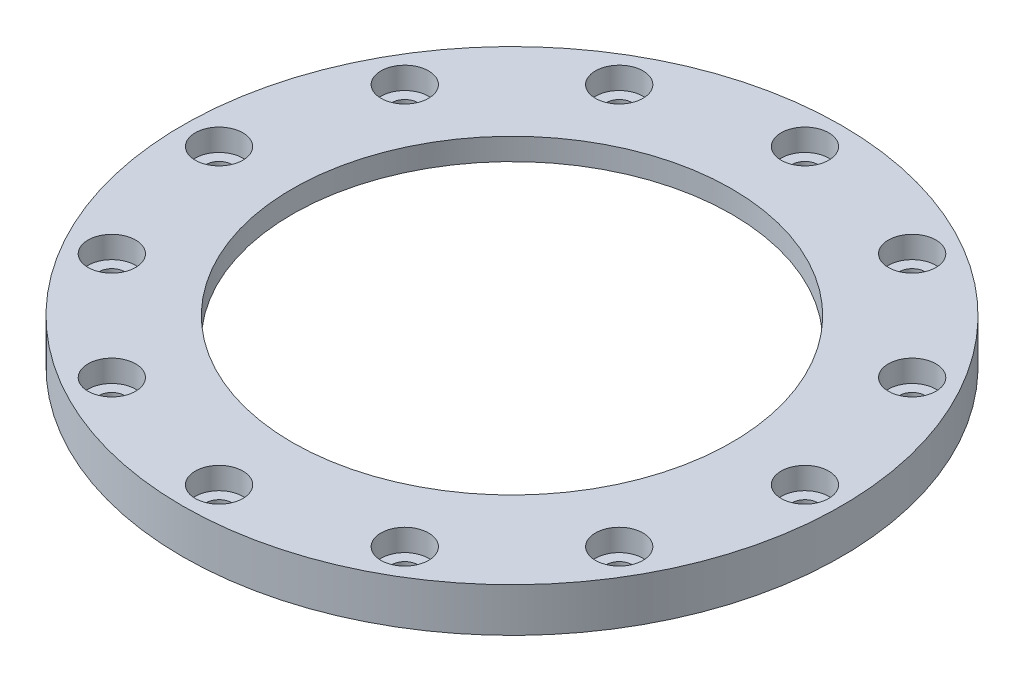
SolidWorks part; units mm, degrees
ref_plane "Front Plane" through (0, 0, 0) normal (0, 0, 1) x (1, 0, 0)
ref_plane "Top Plane" through (0, 0, 0) normal (0, 1, 0) x (1, 0, 0)
ref_plane "Right Plane" through (0, 0, 0) normal (1, 0, 0) x (0, 0, -1)
sketch "Sketch1" plane through (0, 0, 0) normal (0, 1, 0) x (1, 0, 0)
  line L0 (0, 0) -> (0, 52.0165) construction
  circle A0 centre (0, 0) radius 45
  circle A1 centre (0, 0) radius 30
  circle A2 centre (0, 0) radius 40 construction
  circle A3 centre (0, 40) radius 1.75
  circle A4 centre (0, 0) radius 35 construction
  circle A5 centre (20, 34.641) radius 1.75
  circle A6 centre (34.641, 20) radius 1.75
  circle A7 centre (40, 0) radius 1.75
  circle A8 centre (34.641, -20) radius 1.75
  circle A9 centre (20, -34.641) radius 1.75
  circle A10 centre (0, -40) radius 1.75
  circle A11 centre (-20, -34.641) radius 1.75
  circle A12 centre (-34.641, -20) radius 1.75
  circle A13 centre (-40, 0) radius 1.75
  circle A14 centre (-34.641, 20) radius 1.75
  circle A15 centre (-20, 34.641) radius 1.75
  point P21 (0, 0)
  point P34 (0, 0)
  point P48 (0, 0)
  point P72 (0, 0)
  dimension "D1" = 90
  dimension "D2" = 60
  dimension "D4" = 3.5
  dimension "D5" = 70
  dimension "D6" = 12
  dimension "D3" = 80
extrude "Boss-Extrude1" add sketch "Sketch1" along normal blind 6
sketch "Sketch2" plane through (0, 0, 0) normal (0, -1, 0) x (1, 0, 0)
  circle A0 centre (0, 0) radius 35.5
  dimension "D1" = 71
extrude "Cut-Extrude1" cut sketch "Sketch2" against normal blind 3
sketch "Sketch3" plane through (0, 6, 0) normal (0, 1, 0) x (1, 0, 0)
  line L0 (0, 0) -> (49.8808, 0) construction
  circle A0 centre (40, 0) radius 3.25
  circle A1 centre (34.641, -20) radius 3.25
  circle A2 centre (20, -34.641) radius 3.25
  circle A3 centre (0, -40) radius 3.25
  circle A4 centre (-20, -34.641) radius 3.25
  circle A5 centre (-34.641, -20) radius 3.25
  circle A6 centre (-40, 0) radius 3.25
  circle A7 centre (-34.641, 20) radius 3.25
  circle A8 centre (-20, 34.641) radius 3.25
  circle A9 centre (0, 40) radius 3.25
  circle A10 centre (20, 34.641) radius 3.25
  circle A11 centre (34.641, 20) radius 3.25
  point P30 (0, 0)
  dimension "D1" = 6.5
  dimension "D2" = 12
extrude "Cut-Extrude2" cut sketch "Sketch3" against normal blind 3
